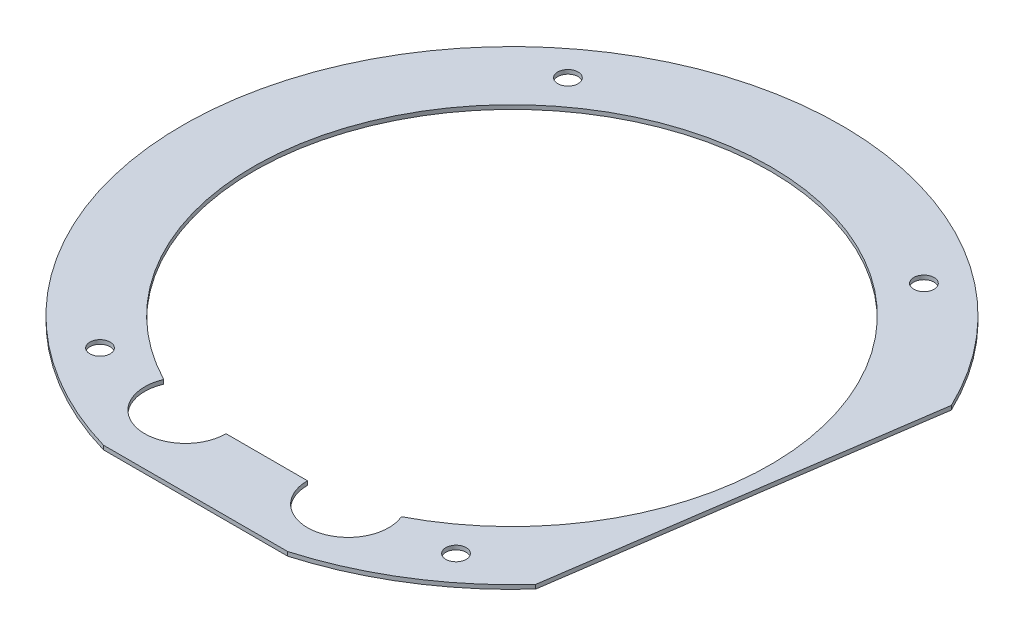
SolidWorks part; units mm, degrees
ref_plane "Front Plane" through (0, 0, 0) normal (0, 0, 1) x (1, 0, 0)
ref_plane "Top Plane" through (0, 0, 0) normal (0, 1, 0) x (1, 0, 0)
ref_plane "Right Plane" through (0, 0, 0) normal (1, 0, 0) x (0, 0, -1)
sketch "Sketch1" plane through (0, 0, 0) normal (0, 1, 0) x (1, 0, 0)
  line L1 (-4, -24.1073) -> (4, -24.1073)
  line L2 (29.2378, 13.961) -> (24.0491, -21.7118)
  line L3 (-9.0608, -31.1073) -> (9.0608, -31.1073)
  arc A0 (11.6854, -22.5524) -> (-11.6854, -22.5524) centre (0, 0) ccw
  circle A1 centre (-17.5, 23) radius 1
  arc A2 (9.0608, -31.1073) -> (24.0491, -21.7118) centre (0, 0) ccw
  arc A3 (29.2378, 13.961) -> (-9.0608, -31.1073) centre (0, 0) ccw
  circle A4 centre (-17.5, -23) radius 1
  circle A5 centre (17.5, -23) radius 1
  circle A6 centre (17.5, 23) radius 1
  arc A7 (-4, -24.1073) -> (-11.6854, -22.5524) centre (-8, -24.1073) cw
  arc A8 (4, -24.1073) -> (11.6854, -22.5524) centre (8, -24.1073) ccw
  dimension "D1" = 2
  dimension "D2" = 2
  dimension "D3" = 2
  dimension "D4" = 2
  dimension "D10" = 7
  dimension "D11" = 25.4
  dimension "D12" = 32.4
  dimension "D15" = 4
  dimension "D16" = 4
  dimension "D5" = 17.5
  dimension "D6" = 23
  dimension "D7" = 46
  dimension "D8" = 35
  dimension "D9" = 7
  dimension "D13" = 16
  dimension "D14" = 36.0481
  dimension "D17" = 8
  dimension "D18" = 7.8411
  dimension "D19" = 7.8411
extrude "Boss-Extrude1" add sketch "Sketch1" along normal blind 0.4
